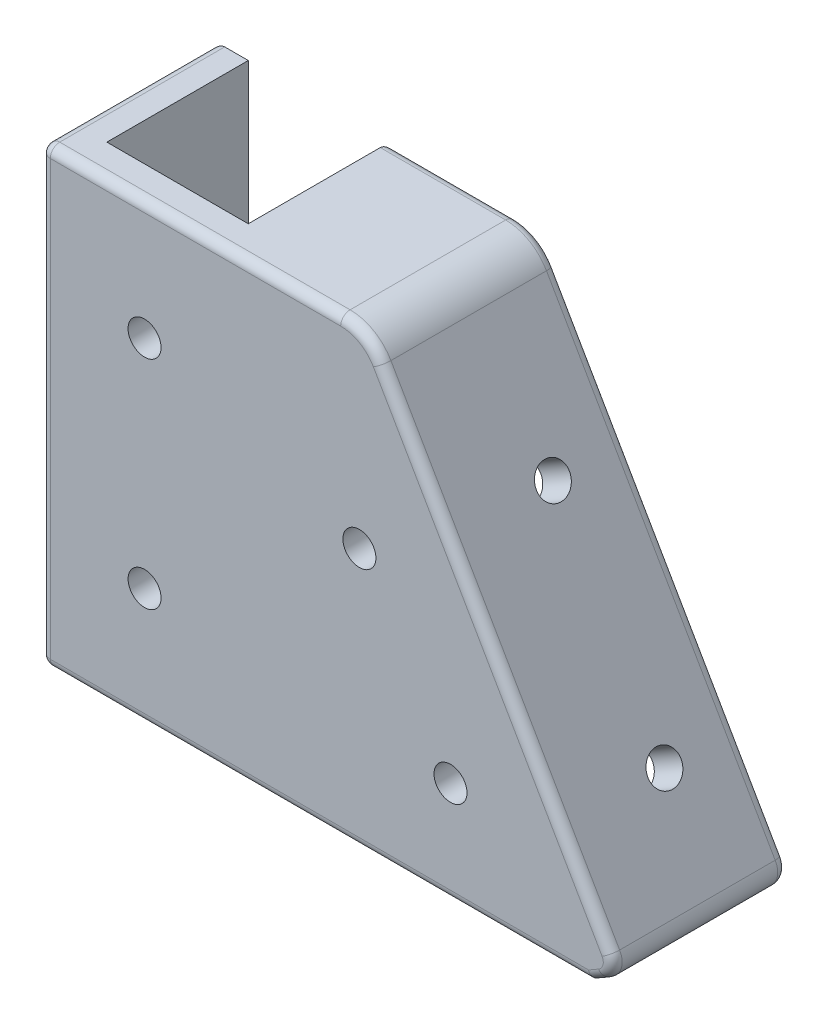
SolidWorks part; units mm, degrees
ref_plane "Front Plane" through (0, 0, 0) normal (0, 0, 1) x (1, 0, 0)
ref_plane "Top Plane" through (0, 0, 0) normal (0, 1, 0) x (1, 0, 0)
ref_plane "Right Plane" through (0, 0, 0) normal (1, 0, 0) x (0, 0, -1)
sketch "Sketch1" plane through (0, 0, 0) normal (0, 0, 1) x (1, 0, 0)
  line L0 (20.5456, 15.4888) -> (48.2584, -32.5112)
  line L2 (-14.145, 15.4888) -> (-14.145, -32.5112)
  line L3 (-14.145, -32.5112) -> (7.855, -32.5112)
  line L4 (7.855, 37.4696) -> (7.855, -32.5112) construction
  line L5 (48.2584, -32.5112) -> (7.855, -32.5112)
  line L6 (22.855, -32.5112) -> (7.855, -6.5304) construction
  line L7 (7.855, -6.5304) -> (44.3314, 14.5292) construction
  line L8 (20.5456, 15.4888) -> (-14.145, 15.4888)
  dimension "D2" = 30
  dimension "D3" = 22
  dimension "D4" = 30
  dimension "D5" = 48
extrude "Boss-Extrude1" add sketch "Sketch1" along normal blind 18.5
sketch "Sketch2" plane through (0, 0, 0) normal (0, 0, 1) x (1, 0, 0)
  line L1 (-14.145, -32.5112) -> (48.2584, -32.5112) construction
  line L2 (-10.645, 15.4888) -> (4.355, 15.4888)
  line L3 (-10.645, 15.4888) -> (-10.645, -32.5112)
  line L4 (-10.645, -32.5112) -> (4.355, -32.5112)
  line L5 (4.355, 15.4888) -> (4.355, -32.5112)
  line L6 (-14.145, 15.4888) -> (-14.145, -32.5112) construction
  line L7 (44.2169, -32.5112) -> (19.8868, 9.6298)
  line L8 (19.8868, 9.6298) -> (6.8964, 2.1298)
  line L9 (6.8964, 2.1298) -> (26.8964, -32.5112)
  line L10 (26.8964, -32.5112) -> (44.2169, -32.5112)
  line L11 (48.2584, -32.5112) -> (20.5456, 15.4888) construction
  line L12 (20.5456, 15.4888) -> (-14.145, 15.4888) construction
  dimension "D1" = 15
  dimension "D2" = 3.5
  dimension "D3" = 3.5
  dimension "D4" = 15
  dimension "D5" = 40
extrude "Cut-Extrude1" cut sketch "Sketch2" along normal offset from surface (15 mm away) 15 up to face at (10.1285, -8.5112, 0)
sketch "Sketch3" plane through (22.116, 12.7687, 0) normal (0.866, 0.5, 0) x (0, 0, -1)
  line L0 (-7.5, 30.2721) -> (-7.5, -52.2847) construction
  line L1 (-15, -1.6038) -> (0, -1.6038) construction
  line L2 (-18.5, -52.2847) -> (0, -52.2847) construction
  line L3 (-15, -50.264) -> (0, -50.264) construction
  circle A0 centre (-7.5, -37.764) radius 1.75
  circle A2 centre (-7.5, -14.1038) radius 1.75
  dimension "D1" = 3.5
  dimension "D2" = 12.5
  dimension "D3" = 12.5
extrude "Cut-Extrude2" cut sketch "Sketch3" against normal blind 3.5
sketch "Sketch4" plane through (0, 0, 18.5) normal (0, 0, -1) x (-1, 0, 0)
  line L0 (3.145, 15.4888) -> (3.145, -32.5112) construction
  line L1 (-20.5456, 15.4888) -> (14.145, 15.4888) construction
  line L2 (14.145, -32.5112) -> (10.645, -32.5112) construction
  line L3 (-13.3916, 5.8798) -> (-35.5567, -32.5112) construction
  line L4 (-6.8964, 2.1298) -> (-19.8868, 9.6298) construction
  line L5 (-19.8868, 9.6298) -> (-6.8964, 2.1298) construction
  line L6 (14.145, 15.4888) -> (14.145, -32.5112) construction
  circle A0 centre (-29.3067, -21.6859) radius 1.75
  circle A2 centre (-19.6416, -4.9455) radius 1.75
  circle A4 centre (3.145, 2.9888) radius 1.75
  circle A6 centre (3.145, -20.0112) radius 1.75
  circle A7 centre (3.145, 14.4888) radius 1.75 [skipped]
  circle A8 centre (3.145, -8.5112) radius 1.75 [skipped]
  dimension "D1" = 12.5
  dimension "D2" = 12.5
  dimension "D4" = 3.5
  dimension "D5" = 4
  dimension "D6" = 12.5
  dimension "D7" = 11
  dimension "D8" = 12.5
extrude "Cut-Extrude3" cut sketch "Sketch4" along normal blind 4
sketch "Sketch5" plane through (-14.145, 0, 0) normal (-1, 0, 0) x (0, 0, 1)
  line L0 (7.5, 39.9696) -> (7.5, -32.5112) construction
  line L2 (18.5, -32.5112) -> (0, -32.5112) construction
  line L3 (18.5, 15.4888) -> (0, 15.4888) construction
  line L4 (0, 15.4888) -> (0, -32.5112) construction
  circle A0 centre (7.5, -20.0112) radius 1.75
  circle A2 centre (7.5, 2.9888) radius 1.75
  circle A4 centre (7.5, 14.4888) radius 1.75 [skipped]
  circle A5 centre (7.5, -8.5112) radius 1.75 [skipped]
  dimension "D2" = 3.5
  dimension "D3" = 12.5
  dimension "D5" = 12.5
  dimension "D1" = 7.5
  dimension "D4" = 4
extrude "Cut-Extrude4" cut sketch "Sketch5" against normal blind 4
sketch "Sketch6" plane through (0, 0, 18.5) normal (0, 0, 1) x (1, 0, 0)
  line L0 (44.2169, -32.5112) -> (47.248, -30.7612)
  line L1 (48.2584, -32.5112) -> (20.5456, 15.4888) construction
  line L2 (47.248, -30.7612) -> (48.2584, -32.5112)
  line L3 (48.2584, -32.5112) -> (44.2169, -32.5112)
extrude "Cut-Extrude5" cut sketch "Sketch6" against normal blind 19
fillet "Fillet1" radius 2 1 edges at (47.248, -30.7612, 9.25)
fillet "Fillet2" radius 5 1 edges at (20.5456, 15.4888, 9.25)
fillet "Fillet3" radius 1 17 edges at (44.8665, -32.1362, 0) (46.4478, -30.5468, 0) (11.0069, 15.4888, 0) (20.1588, 14.8189, 0) (44.8665, -32.1362, 18.5) (46.4478, -30.5468, 18.5) (1.7569, 15.4888, 18.5) (20.1588, 14.8189, 18.5) (-14.145, 15.4888, 9.25) (-14.145, -32.5112, 9.25) (-14.145, -8.5112, 0) (15.6257, -32.5112, 0) (4.355, -8.5112, 0) (34.1185, -8.0202, 0) (-14.145, -8.5112, 18.5) (15.036, -32.5112, 18.5) (34.1185, -8.0202, 18.5)
